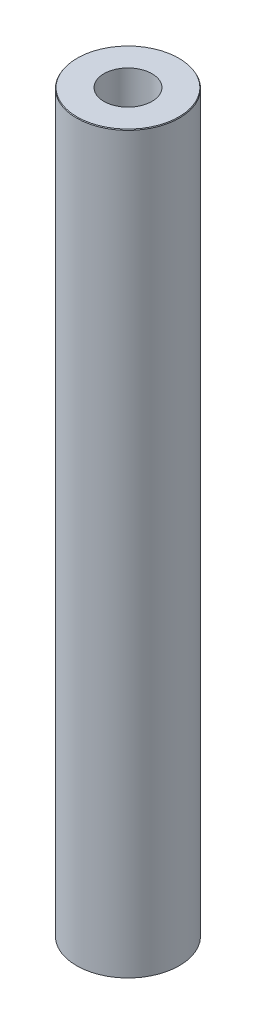
SolidWorks part; units mm, degrees
ref_plane "Front Plane" through (0, 0, 0) normal (0, 0, 1) x (1, 0, 0)
ref_plane "Top Plane" through (0, 0, 0) normal (0, 1, 0) x (1, 0, 0)
ref_plane "Right Plane" through (0, 0, 0) normal (1, 0, 0) x (0, 0, -1)
sketch "Sketch1" plane through (0, 0, 0) normal (0, 1, 0) x (1, 0, 0)
  circle A0 centre (0, 0) radius 35
  dimension "SHAFT_OD" = 70
extrude "Boss-Extrude1" add sketch "Sketch1" along normal blind 501.1939
sketch "Sketch2" plane through (0, 0, 0) normal (0, 1, 0) x (1, 0, 0)
  circle A0 centre (0, 0) radius 16.3827
  dimension "BORE_D" = 32.7654
extrude "Cut-Extrude1" cut sketch "Sketch2" along normal through all
chamfer "Chamfer1" distance 0.5566 angle 30 2 edges at (0, 501.1939, 35) (0, 0, 35) first distance on face at (0, 501.1939, 35) first distance on face at (0, 0, 16.3827)
